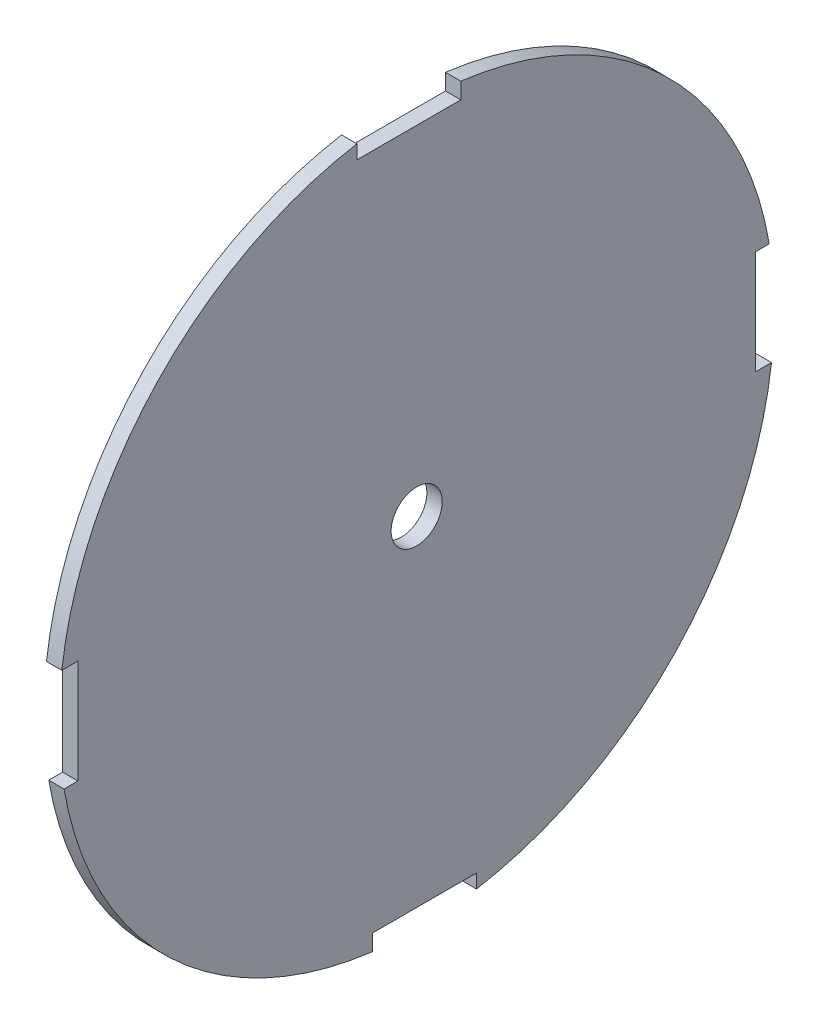
SolidWorks part; units mm, degrees
material "AISI 304"
ref_plane "Front Plane" through (0, 0, 0) normal (0, 0, 1) x (1, 0, 0)
ref_plane "Top Plane" through (0, 0, 0) normal (0, 1, 0) x (1, 0, 0)
ref_plane "Right Plane" through (0, 0, 0) normal (1, 0, 0) x (0, 0, -1)
sketch "Sketch1" plane through (0, 0, 0) normal (1, 0, 0) x (0, 0, -1)
  line L5 (0, 0) -> (0, 35) construction
  line L22 (-34.7323, 4.3205) -> (-33.15, 4.3205)
  line L23 (-33.15, 4.3205) -> (-33.15, -5.85)
  line L47 (-34.5076, -5.85) -> (-33.15, -5.85)
  line L55 (-4.3205, -34.7323) -> (-4.3205, -33.15)
  line L56 (-4.3205, -33.15) -> (5.85, -33.15)
  line L57 (5.85, -34.5076) -> (5.85, -33.15)
  line L61 (4.3205, 34.7323) -> (4.3205, 33.15)
  line L62 (4.3205, 33.15) -> (-5.85, 33.15)
  line L63 (-5.85, 34.5076) -> (-5.85, 33.15)
  line L64 (34.7323, -4.3205) -> (33.15, -4.3205)
  line L65 (33.15, -4.3205) -> (33.15, 5.85)
  line L66 (34.5076, 5.85) -> (33.15, 5.85)
  line L70 (5.75, -34.75) -> (5.75, -33.25) construction
  line L71 (-4.2205, -34.75) -> (-4.2205, -33.25) construction
  line L72 (3.75, -33.25) -> (5.75, -33.25) construction
  circle A1 centre (0, 0) radius 2.5
  circle A2 centre (0, 0) radius 40 construction
  arc A7 (5.85, -34.5076) -> (34.7323, -4.3205) centre (0, 0) ccw
  arc A8 (34.5076, 5.85) -> (4.3205, 34.7323) centre (0, 0) ccw
  arc A9 (-5.85, 34.5076) -> (-34.7323, 4.3205) centre (0, 0) ccw
  arc A10 (-34.5076, -5.85) -> (-4.3205, -34.7323) centre (0, 0) ccw
  point P27 (0, 0)
  point P31 (0, 0)
  point P38 (0, 0)
  dimension "D6" = 5
  dimension "D7" = 0.1
  dimension "D5" = 80
  dimension "D1" = 70
  dimension "D2" = 4
  dimension "D3" = 0.1
  dimension "D4" = 0.1
extrude "Boss-Extrude3" add sketch "Sketch1" along normal blind 1.5
